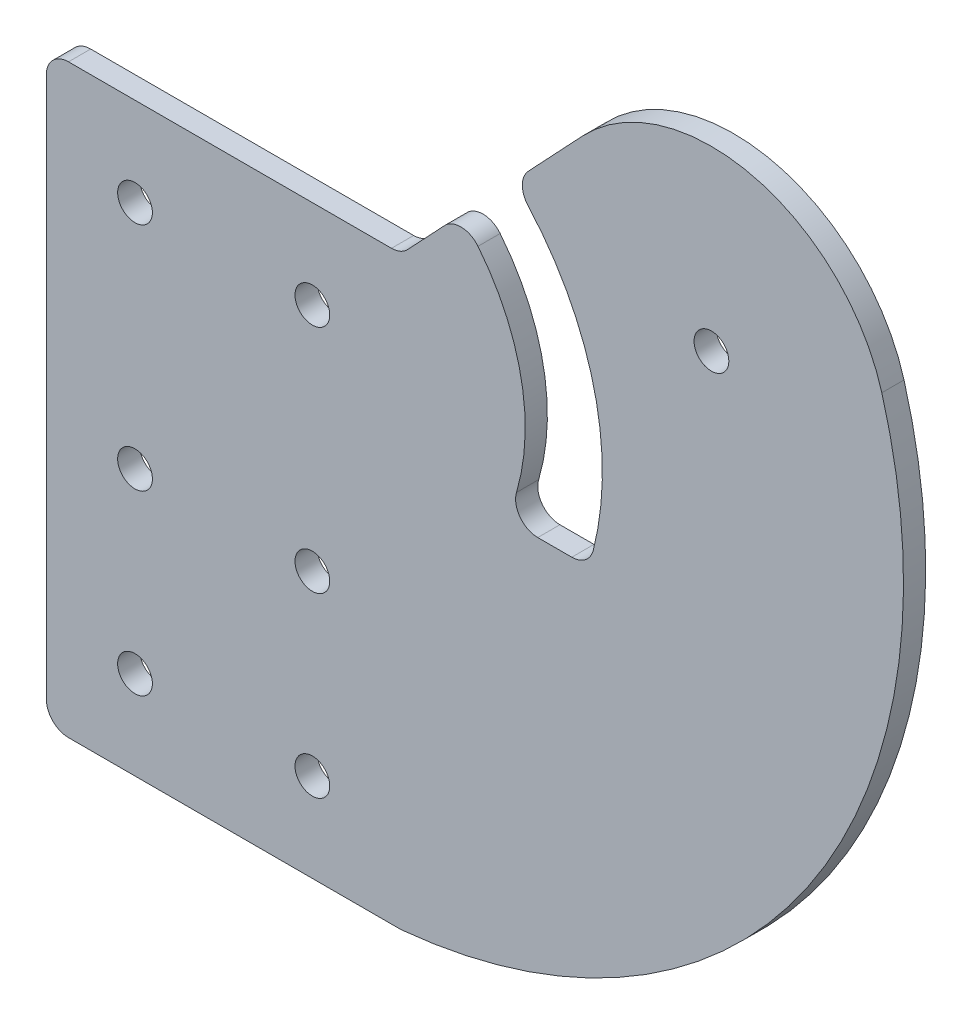
SolidWorks part; units mm, degrees
material "6061-T6 (SS)"
ref_plane "Front Plane" through (0, 0, 0) normal (0, 0, 1) x (1, 0, 0)
ref_plane "Top Plane" through (0, 0, 0) normal (0, 1, 0) x (1, 0, 0)
ref_plane "Right Plane" through (0, 0, 0) normal (1, 0, 0) x (0, 0, -1)
sketch "Sketch2" plane through (0, 0, 0) normal (0, 0, 1) x (1, 0, 0)
  line L0 (50.8, 83.82) -> (59.1187, 92.6561)
  line L1 (0, 0) -> (50.8, 0)
  line L2 (0, 0) -> (0, 83.82)
  line L3 (0, 83.82) -> (50.8, 83.82)
  line L11 (59.1187, 92.6561) -> (59.384, 92.938)
  line L12 (65.8081, 58.42) -> (77.6394, 58.42)
  line L14 (76.7561, 111.3908) -> (66.9585, 100.9837)
  circle A2 centre (95.25, 93.98) radius 2.4892
  arc A3 (50.8, 0) -> (119.656, 101.0162) centre (43.3873, 79.0281) ccw
  circle A4 centre (38.1, 71.12) radius 2.4892 construction
  circle A5 centre (13.208, 97.028) radius 4.7625 construction
  arc A8 (119.656, 101.0162) -> (76.7561, 111.3908) centre (95.25, 93.98) ccw
  arc A9 (65.8081, 58.42) -> (59.384, 92.938) centre (38.1, 71.12) ccw
  arc A10 (77.6394, 58.42) -> (66.9585, 100.9837) centre (38.1, 71.12) ccw
  dimension "D3" = 50.8
  dimension "D5" = 95.25
  dimension "D4" = 4.9784
  dimension "D7" = 158.75
  dimension "D11" = 4.9784
  dimension "D8" = 60.96
  dimension "D9" = 83.058
  dimension "D16" = 9.525
  dimension "D1" = 50.8
  dimension "D2" = 83.82
  dimension "D6" = 93.98
  dimension "D10" = 25.4
  dimension "D12" = 38.1
  dimension "D13" = 12.7
  dimension "D14" = 25.908
  dimension "D15" = 24.892
extrude "Boss-Extrude1" add sketch "Sketch2" against normal blind 3.175
sketch "Sketch3" plane through (0, 0, 0) normal (0, 0, 1) x (1, 0, 0)
  line L0 (50.8, 83.82) -> (0, 83.82) construction
  line L1 (0, 83.82) -> (0, 0) construction
  circle A0 centre (12.7, 71.12) radius 2.4892
  circle A17 centre (38.1, 71.12) radius 2.4892
  circle A24 centre (12.7, 38.1) radius 2.4892
  circle A25 centre (12.7, 12.7) radius 2.4892
  circle A26 centre (12.7, -12.7) radius 2.4892
  circle A27 centre (12.7, -38.1) radius 2.4892
  circle A28 centre (12.7, -63.5) radius 2.4892
  circle A33 centre (38.1, 12.7) radius 2.4892
  circle A34 centre (38.1, -12.7) radius 2.4892
  circle A35 centre (38.1, -38.1) radius 2.4892
  circle A36 centre (38.1, -63.5) radius 2.4892
  circle A41 centre (38.1, 38.1) radius 2.4892
  dimension "D1" = 4.9784
  dimension "D6" = 4.9784
  dimension "D2" = 12.7
  dimension "D3" = 12.7
  dimension "D7" = 12.7
  dimension "D8" = 33.02
  dimension "D4" = 1
  dimension "D5" = 2
  dimension "D9" = 5
  dimension "D10" = 2
extrude "Cut-Extrude1" cut sketch "Sketch3" against normal through all
fillet "Fillet1" radius 3.175 8 edges at (0, 0, -1.5875) (50.8, 83.82, -1.5875) (0, 83.82, -1.5875) (50.8, 0, -1.5875) (77.6394, 58.42, -1.5875) (65.8081, 58.42, -1.5875) (59.384, 92.938, -1.5875) (66.9585, 100.9837, -1.5875)
